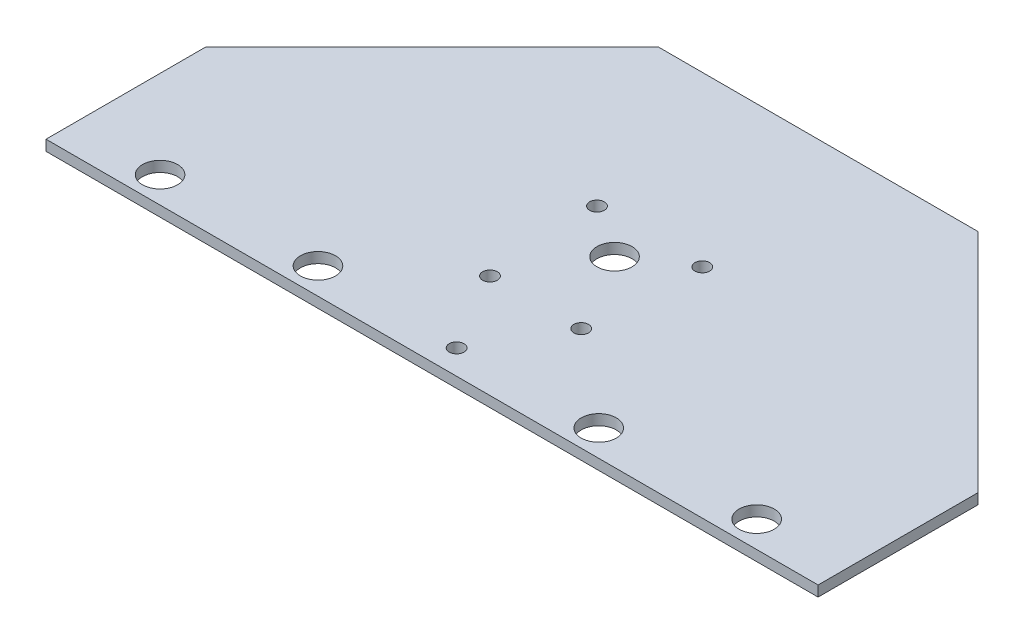
SolidWorks part; units mm, degrees
material "Plain Carbon Steel"
ref_plane "Front" through (0, 0, 0) normal (0, 0, 1) x (1, 0, 0)
ref_plane "Top" through (0, 0, 0) normal (0, 1, 0) x (1, 0, 0)
ref_plane "Right" through (0, 0, 0) normal (1, 0, 0) x (0, 0, -1)
ref_plane "Plane1" through (0, 0, 0) normal (0, 1, 0) x (1, 0, 0)
ref_axis "Axis1" through (0, 62.7688, 0) along (0, -1, 0)
ref_plane "Plane2" through (0, 0, 0) normal (0, 0, -1) x (-1, 0, 0)
sketch "Sketch1" plane through (0, 0, 0) normal (0, 1, 0) x (1, 0, 0)
  line L0 (0, 0) -> (0, -34.3815) construction
  line L1 (0, -13.9474) -> (0, 96.0526) construction
  line L2 (0, 96.0526) -> (0, 144.8013) construction
  line L3 (-110, -13.9474) -> (-110, 31.6161)
  line L4 (-110, -13.9474) -> (110, -13.9474)
  line L5 (-110, 31.6161) -> (-45.5635, 96.0526)
  line L6 (-45.5635, 96.0526) -> (0, 96.0526)
  line L7 (0, 96.0526) -> (45.5635, 96.0526)
  line L8 (45.5635, 96.0526) -> (110, 31.6161)
  line L9 (110, 31.6161) -> (110, -13.9474)
  arc A0 (-110, -13.9474) -> (110, -13.9474) centre (0, -13.9474) cw construction
  point P9 (0, -13.9474)
  dimension "D1" = 110
  dimension "D2" = 45
  dimension "D3" = 91.127
  dimension "D4" = 45.5635
extrude "Extrude1" add sketch "Sketch1" along normal blind 3
sketch "Sketch2" plane through (0, 3, 0) normal (0, 1, 0) x (-1, 0, 0)
  line L0 (0, 0) -> (0, -41.4225) construction
  line L1 (0, 0) -> (0, 32.8119) construction
  line L2 (85, 6.4474) -> (40, 6.4474) construction
  line L3 (40, 6.4474) -> (0, 6.4474) construction
  line L4 (0, 6.4474) -> (-40, 6.4474) construction
  line L5 (-40, 6.4474) -> (-85, 6.4474) construction
  line L6 (110, 13.9474) -> (-110, 13.9474) construction
  circle A0 centre (85, 6.4474) radius 5
  circle A1 centre (40, 6.4474) radius 5
  circle A3 centre (-40, 6.4474) radius 5
  circle A4 centre (-85, 6.4474) radius 5
  dimension "D1" = 10
  dimension "D2" = 40
  dimension "D3" = 45
  dimension "D4" = 7.5
extrude "Cut-Extrude1" cut sketch "Sketch2" against normal through all
sketch "Sketch3" [suppressed] plane through (0, 3, 0) normal (0, 1, 0) x (-1, 0, 0)
  line L0 (110, 13.9474) -> (-110, 13.9474) construction
  line L1 (0, 13.9474) -> (-144.6051, 13.9474)
  line L2 (0, 13.9474) -> (0, -110.5857)
  line L3 (0, -110.5857) -> (-144.6051, -110.5857)
  line L4 (-144.6051, 13.9474) -> (-144.6051, -110.5857)
extrude "Cut-Extrude2" [suppressed] cut sketch "Sketch3" against normal through all
sketch "Sketch4" [suppressed] plane through (0, 3, 0) normal (0, 1, 0) x (-1, 0, 0)
  line L1 (0, 13.9474) -> (30, 13.9474)
  line L2 (0, 13.9474) -> (0, -16.0526)
  line L3 (0, -16.0526) -> (30, -16.0526)
  line L4 (30, 13.9474) -> (30, -16.0526)
  dimension "D1" = 30
extrude "Cut-Extrude3" [suppressed] cut sketch "Sketch4" against normal through all
sketch "Sketch5" [suppressed] plane through (0, 3, 0) normal (0, 1, 0) x (-1, 0, 0)
  line L1 (110, 13.9474) -> (30, 13.9474) construction
  line L2 (0, -96.0526) -> (0, -16.0526) construction
  circle A0 centre (67.5, -42.5326) radius 5
  dimension "D1" = 10
  dimension "D2" = 67.5
  dimension "D3" = 56.48
extrude "Cut-Extrude4" [suppressed] cut sketch "Sketch5" against normal through all
sketch "Sketch6" [suppressed] plane through (0, 3, 0) normal (0, 1, 0) x (-1, 0, 0)
  line L0 (67.5, -42.5326) -> (72.5, -51.1929) construction
  line L1 (67.5, -42.5326) -> (45, -3.5615) construction
  line L2 (0, -96.0526) -> (0, -16.0526) construction
  line L3 (72.5, -51.1929) -> (59.5096, -58.6929) construction
  line L4 (72.5, -51.1929) -> (85.4904, -43.6929) construction
  line L5 (56.25, -23.047) -> (67.4997, -16.552) construction
  line L6 (56.25, -23.047) -> (45.0003, -29.542) construction
  circle A0 centre (85.4904, -43.6929) radius 2.1
  circle A1 centre (59.5096, -58.6929) radius 2.1
  circle A2 centre (45.0003, -29.542) radius 2.1
  circle A3 centre (67.4997, -16.552) radius 2.1
  circle A4 centre (45, -3.5615) radius 2.1
  circle A5 centre (67.5, -42.5326) radius 5 construction
  dimension "D2" = 4.2
  dimension "D3" = 30
  dimension "D4" = 10
  dimension "D5" = 45
  dimension "D6" = 22.5
  dimension "D7" = 25.98
  dimension "D1" = 30
extrude "Cut-Extrude5" [suppressed] cut sketch "Sketch6" against normal through all
sketch "Sketch7" plane through (0, 3, 0) normal (0, 1, 0) x (-1, 0, 0)
  line L0 (0, 13.9474) -> (0, -38.0526) construction
  line L1 (110, 13.9474) -> (-110, 13.9474) construction
  circle A0 centre (0, -38.0526) radius 5
  dimension "D1" = 10
  dimension "D2" = 52
extrude "Cut-Extrude6" cut sketch "Sketch7" against normal through all
sketch "Sketch8" plane through (49.2674, 3, 2.6714) normal (0, 1, 0) x (-1, 0, 0)
  line L0 (49.2674, -40.7241) -> (49.2674, -50.7241) construction
  line L1 (49.2674, -40.7241) -> (49.2674, 4.2759) construction
  line L3 (49.2674, -50.7241) -> (34.2674, -50.7241) construction
  line L4 (49.2674, -50.7241) -> (64.2674, -50.7241) construction
  line L5 (49.2674, -18.2241) -> (62.2574, -18.2241) construction
  line L6 (49.2674, -18.2241) -> (36.2774, -18.2241) construction
  line L7 (159.2674, 11.2759) -> (-60.7326, 11.2759) construction
  circle A0 centre (64.2674, -50.7241) radius 2.1
  circle A1 centre (34.2674, -50.7241) radius 2.1
  circle A2 centre (36.2774, -18.2241) radius 2.1
  circle A3 centre (62.2574, -18.2241) radius 2.1
  circle A4 centre (49.2674, 4.2759) radius 2.1
  circle A6 centre (49.2674, -40.7241) radius 5 construction
  dimension "D2" = 4.2
  dimension "D3" = 30
  dimension "D4" = 55
  dimension "D5" = 90
  dimension "D6" = 10
  dimension "D7" = 25.98
  dimension "D8" = 22.5
  dimension "D9" = 45
  dimension "D1" = 32.5
extrude "Cut-Extrude7" cut sketch "Sketch8" against normal through all
ref_axis "Axis2" through (0, 3, -38.0526) along (0, -1, 0)
ref_plane "Plane3" through (0, 0, 0) normal (1, 0, 0) x (0, 0, -1)
ref_axis "Axis3" [suppressed] through (-67.5, 3, -42.5326) along (0, -1, 0)
